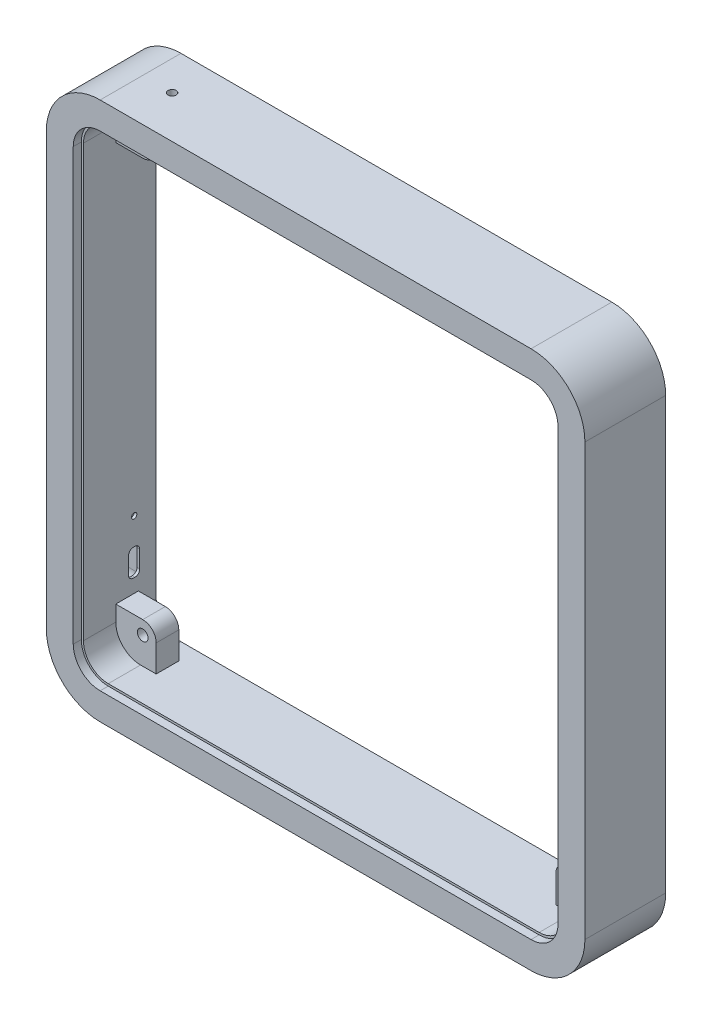
SolidWorks part; units mm, degrees
ref_plane "Piano frontale" through (0, 0, 0) normal (0, 0, 1) x (1, 0, 0)
ref_plane "Piano superiore" through (0, 0, 0) normal (0, 1, 0) x (1, 0, 0)
ref_plane "Piano destro" through (0, 0, 0) normal (1, 0, 0) x (0, 0, -1)
sketch "Sketch2" plane through (0, 0, 0) normal (0, 0, 1) x (1, 0, 0)
  line L5 (-100, -100) -> (100, -100)
  line L6 (-100, -100) -> (-100, 100)
  line L7 (-100, 100) -> (100, 100)
  line L8 (100, -100) -> (100, 100)
  line L9 (-100, -100) -> (100, 100) construction
  line L10 (-100, 100) -> (100, -100) construction
  point P0 (0, 0)
  dimension "D1" = 200
extrude "Boss-Extrude1" add sketch "Sketch2" along normal blind 30
fillet "Fillet1" radius 20 4 edges at (-100, -100, 15) (100, -100, 15) (100, 100, 15) (-100, 100, 15)
sketch "Sketch3" plane through (0, 0, 30) normal (0, 0, 1) x (1, 0, 0)
  line L8 (-90, 80) -> (-90, -80)
  line L9 (-80, -90) -> (80, -90)
  line L10 (90, -80) -> (90, 80)
  line L11 (80, 90) -> (-80, 90)
  line L12 (-90, 80) -> (-90, -80)
  line L13 (-80, -90) -> (80, -90)
  line L14 (90, -80) -> (90, 80)
  line L15 (80, 90) -> (-80, 90)
  arc A8 (-90, -80) -> (-80, -90) centre (-80, -80) ccw
  arc A9 (80, -90) -> (90, -80) centre (80, -80) ccw
  arc A10 (90, 80) -> (80, 90) centre (80, 80) ccw
  arc A11 (-80, 90) -> (-90, 80) centre (-80, 80) ccw
  arc A12 (-90, -80) -> (-80, -90) centre (-80, -80) ccw
  arc A13 (80, -90) -> (90, -80) centre (80, -80) ccw
  arc A14 (90, 80) -> (80, 90) centre (80, 80) ccw
  arc A15 (-80, 90) -> (-90, 80) centre (-80, 80) ccw
  dimension "D1" = 10
extrude "Cut-Extrude1" cut sketch "Sketch3" against normal blind 3
sketch "Sketch4" plane through (0, 0, 27) normal (0, 0, 1) x (1, 0, 0)
  line L16 (-89.2, 80) -> (-89.2, -80)
  line L17 (-80, -89.2) -> (80, -89.2)
  line L18 (89.2, -80) -> (89.2, 80)
  line L19 (80, 89.2) -> (-80, 89.2)
  line L20 (-89.2, 80) -> (-89.2, -80)
  line L21 (-80, -89.2) -> (80, -89.2)
  line L22 (89.2, -80) -> (89.2, 80)
  line L23 (80, 89.2) -> (-80, 89.2)
  arc A16 (-80, 89.2) -> (-89.2, 80) centre (-80, 80) ccw
  arc A17 (-89.2, -80) -> (-80, -89.2) centre (-80, -80) ccw
  arc A18 (80, -89.2) -> (89.2, -80) centre (80, -80) ccw
  arc A19 (89.2, 80) -> (80, 89.2) centre (80, 80) ccw
  arc A20 (-80, 89.2) -> (-89.2, 80) centre (-80, 80) ccw
  arc A21 (-89.2, -80) -> (-80, -89.2) centre (-80, -80) ccw
  arc A22 (80, -89.2) -> (89.2, -80) centre (80, -80) ccw
  arc A23 (89.2, 80) -> (80, 89.2) centre (80, 80) ccw
  dimension "D1" = 0.8
extrude "Cut-Extrude2" cut sketch "Sketch4" against normal through all
sketch "Sketch6" plane through (0, 0, 0) normal (0, 0, -1) x (-1, 0, 0)
  line L1 (-89.2, -74.2) -> (-74.2, -74.2)
  line L2 (-89.2, -74.2) -> (-89.2, -89.2)
  line L3 (-89.2, -89.2) -> (-74.2, -89.2)
  line L4 (-74.2, -74.2) -> (-74.2, -89.2)
  line L5 (-89.2, -80) -> (-89.2, 80) construction
  line L6 (80, -89.2) -> (-80, -89.2) construction
  line L18 (-74.2, 89.2) -> (-74.2, 74.2)
  line L19 (-89.2, 89.2) -> (89.2, 89.2) construction
  line L20 (-89.2, 89.2) -> (-89.2, -89.2) construction
  line L21 (-89.2, -89.2) -> (89.2, -89.2) construction
  line L22 (89.2, 89.2) -> (89.2, -89.2) construction
  line L23 (-89.2, 89.2) -> (89.2, -89.2) construction
  line L24 (-89.2, -89.2) -> (89.2, 89.2) construction
  line L25 (-74.2, 74.2) -> (-89.2, 74.2)
  line L26 (-89.2, 89.2) -> (-89.2, 74.2)
  line L27 (-74.2, 89.2) -> (-89.2, 89.2)
  line L28 (89.2, 74.2) -> (74.2, 74.2)
  line L29 (74.2, 74.2) -> (74.2, 89.2)
  line L30 (89.2, 89.2) -> (74.2, 89.2)
  line L31 (89.2, 74.2) -> (89.2, 89.2)
  line L32 (74.2, -89.2) -> (74.2, -74.2)
  line L33 (74.2, -74.2) -> (89.2, -74.2)
  line L34 (89.2, -89.2) -> (89.2, -74.2)
  line L35 (74.2, -89.2) -> (89.2, -89.2)
  point P14 (0, 0)
  point P19 (0, 0)
  point P24 (0, 0)
  point P29 (0, 0)
  dimension "D2" = 4
  dimension "D1" = 15
extrude "Boss-Extrude4" add sketch "Sketch6" against normal blind 15
fillet "Fillet2" radius 5 4 edges at (74.2, -74.2, 7.5) (-74.2, -74.2, 7.5) (-74.2, 74.2, 7.5) (74.2, 74.2, 7.5)
hole_wizard "Ø4.0 (4) Diameter Hole1" positions "Sketch8" profile "Sketch9" hole size "Ø4.0" standard "ANSI Metric" end condition through all
sketch "Sketch8" plane through (0, 0, 0) normal (0, 0, -1) x (-1, 0, 0)
  point P0 (-79.2, 79.2)
  point P3 (79.2, 79.2)
  point P6 (-79.2, -79.2)
  point P9 (79.2, -79.2)
sketch "Sketch9" plane through (79.2, 79.2, 0) normal (1, 0, 0) x (0, 1, 0)
  line L0 (0, 0) -> (0, 30)
  line L1 (0, 30) -> (2, 30)
  line L2 (2, 30) -> (2, 0)
  line L5 (2, 0) -> (0, 0)
  line L11 (0, -6.35) -> (0, 107.95) construction
  dimension "Thru Hole Dia." = 4
  dimension "Thru Hole Depth" = 30
sketch "Sketch10" plane through (0, 0, 0) normal (0, 0, -1) x (-1, 0, 0)
  line L0 (89.2, -80) -> (89.2, 80)
  line L1 (80, 89.2) -> (-80, 89.2)
  line L2 (-89.2, 80) -> (-89.2, -80)
  line L3 (-80, -89.2) -> (80, -89.2)
  line L4 (90, -80) -> (90, 80)
  line L5 (-80, -90) -> (80, -90)
  line L6 (-90, 80) -> (-90, -80)
  line L7 (80, 90) -> (-80, 90)
  line L8 (90, -80) -> (90, 80) construction
  line L9 (-80, -90) -> (80, -90) construction
  line L10 (-90, 80) -> (-90, -80) construction
  line L11 (80, 90) -> (-80, 90) construction
  arc A0 (89.2, 80) -> (80, 89.2) centre (80, 80) ccw
  arc A1 (-80, 89.2) -> (-89.2, 80) centre (-80, 80) ccw
  arc A2 (-89.2, -80) -> (-80, -89.2) centre (-80, -80) ccw
  arc A3 (80, -89.2) -> (89.2, -80) centre (80, -80) ccw
  arc A4 (90, 80) -> (80, 90) centre (80, 80) ccw
  arc A5 (80, -90) -> (90, -80) centre (80, -80) ccw
  arc A6 (-90, -80) -> (-80, -90) centre (-80, -80) ccw
  arc A7 (-80, 90) -> (-90, 80) centre (-80, 80) ccw
  arc A8 (90, 80) -> (80, 90) centre (80, 80) ccw construction
  arc A9 (80, -90) -> (90, -80) centre (80, -80) ccw construction
  arc A10 (-90, -80) -> (-80, -90) centre (-80, -80) ccw construction
  arc A11 (-80, 90) -> (-90, 80) centre (-80, 80) ccw construction
  dimension "D1" = 0
  dimension "D2" = 0.8
extrude "Cut-Extrude3" cut sketch "Sketch10" against normal blind 6.6
sketch "Sketch11" plane through (0, 100, 0) normal (0, 1, 0) x (1, 0, 0)
  circle A0 centre (-68.955, -14.3249) radius 1.5
extrude "Cut-Extrude4" cut sketch "Sketch11" against normal up to next
sketch "Sketch15" plane through (-89.2, 0, 0) normal (1, 0, 0) x (0, 0, -1)
  line L0 (-6.6, -64.1785) -> (-6.6, -64.1485) construction
  line L1 (-6.1, -64.1785) -> (-6.1, -64.1485)
  line L2 (-6.1, -64.1485) -> (-6.1, -60.9885)
  line L3 (-7.9, -59.1885) -> (-8.46, -59.1885)
  line L4 (-10.26, -60.9885) -> (-10.26, -67.3385)
  line L5 (-8.46, -69.1385) -> (-7.9, -69.1385)
  line L6 (-6.1, -67.3385) -> (-6.1, -64.1785)
  line L7 (-8.18, -49.2385) -> (-8.18, -69.1385) construction
  line L12 (-9.76, -60.9885) -> (-9.76, -67.3385)
  line L13 (-7.9, -59.6885) -> (-8.46, -59.6885)
  line L14 (-6.6, -64.1485) -> (-6.6, -60.9885)
  line L15 (-6.75, -64.1485) -> (-6.6, -64.1485)
  line L16 (-6.75, -60.9885) -> (-6.75, -64.1485)
  line L17 (-8.46, -59.8385) -> (-7.9, -59.8385)
  line L18 (-9.61, -67.3385) -> (-9.61, -60.9885)
  line L19 (-7.9, -68.4885) -> (-8.46, -68.4885)
  line L20 (-6.75, -64.1785) -> (-6.75, -67.3385)
  line L21 (-6.6, -64.1785) -> (-6.75, -64.1785)
  line L22 (-6.6, -67.3385) -> (-6.6, -64.1785)
  line L23 (-8.46, -68.6385) -> (-7.9, -68.6385)
  line L24 (-9.76, -60.9885) -> (-9.76, -67.3385) construction
  line L25 (-7.9, -59.6885) -> (-8.46, -59.6885) construction
  line L26 (-6.6, -64.1485) -> (-6.6, -60.9885) construction
  line L34 (-6.6, -67.3385) -> (-6.6, -64.1785) construction
  line L35 (-8.46, -68.6385) -> (-7.9, -68.6385) construction
  arc A0 (-6.1, -60.9885) -> (-6.6272, -59.7157) centre (-7.9, -60.9885) ccw
  arc A1 (-6.6272, -59.7157) -> (-7.9, -59.1885) centre (-7.9, -60.9885) ccw
  arc A2 (-8.46, -59.1885) -> (-9.7328, -59.7157) centre (-8.46, -60.9885) ccw
  arc A3 (-9.7328, -59.7157) -> (-10.26, -60.9885) centre (-8.46, -60.9885) ccw
  arc A4 (-10.26, -67.3385) -> (-9.7328, -68.6112) centre (-8.46, -67.3385) ccw
  arc A5 (-9.7328, -68.6112) -> (-8.46, -69.1385) centre (-8.46, -67.3385) ccw
  arc A6 (-7.9, -69.1385) -> (-6.6272, -68.6112) centre (-7.9, -67.3385) ccw
  arc A7 (-6.6272, -68.6112) -> (-6.1, -67.3385) centre (-7.9, -67.3385) ccw
  circle A9 centre (-8.18, -49.2385) radius 1
  arc A16 (-9.3792, -68.2577) -> (-8.46, -68.6385) centre (-8.46, -67.3385) ccw
  arc A17 (-9.76, -67.3385) -> (-9.3792, -68.2577) centre (-8.46, -67.3385) ccw
  arc A18 (-9.3792, -60.0692) -> (-9.76, -60.9885) centre (-8.46, -60.9885) ccw
  arc A19 (-8.46, -59.6885) -> (-9.3792, -60.0692) centre (-8.46, -60.9885) ccw
  arc A20 (-6.9808, -60.0692) -> (-7.9, -59.6885) centre (-7.9, -60.9885) ccw
  arc A21 (-6.6, -60.9885) -> (-6.9808, -60.0692) centre (-7.9, -60.9885) ccw
  arc A22 (-6.75, -60.9885) -> (-7.0868, -60.1753) centre (-7.9, -60.9885) ccw
  arc A23 (-7.0868, -60.1753) -> (-7.9, -59.8385) centre (-7.9, -60.9885) ccw
  arc A24 (-8.46, -59.8385) -> (-9.2732, -60.1753) centre (-8.46, -60.9885) ccw
  arc A25 (-9.2732, -60.1753) -> (-9.61, -60.9885) centre (-8.46, -60.9885) ccw
  arc A26 (-9.61, -67.3385) -> (-9.2732, -68.1516) centre (-8.46, -67.3385) ccw
  arc A27 (-9.2732, -68.1516) -> (-8.46, -68.4885) centre (-8.46, -67.3385) ccw
  arc A28 (-7.9, -68.4885) -> (-7.0868, -68.1516) centre (-7.9, -67.3385) ccw
  arc A29 (-7.0868, -68.1516) -> (-6.75, -67.3385) centre (-7.9, -67.3385) ccw
  arc A30 (-6.9808, -68.2577) -> (-6.6, -67.3385) centre (-7.9, -67.3385) ccw
  arc A31 (-7.9, -68.6385) -> (-6.9808, -68.2577) centre (-7.9, -67.3385) ccw
  arc A32 (-9.3792, -68.2577) -> (-8.46, -68.6385) centre (-8.46, -67.3385) ccw construction
  arc A33 (-9.76, -67.3385) -> (-9.3792, -68.2577) centre (-8.46, -67.3385) ccw construction
  arc A34 (-9.3792, -60.0692) -> (-9.76, -60.9885) centre (-8.46, -60.9885) ccw construction
  arc A35 (-8.46, -59.6885) -> (-9.3792, -60.0692) centre (-8.46, -60.9885) ccw construction
  arc A36 (-6.9808, -60.0692) -> (-7.9, -59.6885) centre (-7.9, -60.9885) ccw construction
  arc A37 (-6.6, -60.9885) -> (-6.9808, -60.0692) centre (-7.9, -60.9885) ccw construction
  arc A46 (-6.9808, -68.2577) -> (-6.6, -67.3385) centre (-7.9, -67.3385) ccw construction
  arc A47 (-7.9, -68.6385) -> (-6.9808, -68.2577) centre (-7.9, -67.3385) ccw construction
  point P73 (-8.18, -59.6885)
  point P74 (-8.18, -59.1885)
  dimension "D3" = 2
  dimension "D1" = 0
  dimension "D2" = 0.5
extrude "Cut-Extrude5" cut sketch "Sketch15" against normal through all
sketch "Sketch16" plane through (-100, 0, 0) normal (-1, 0, 0) x (0, 0, 1)
  line L0 (6.1, -67.3385) -> (6.1, -60.9885) construction
  line L1 (7.9, -59.1885) -> (8.46, -59.1885) construction
  line L2 (10.26, -60.9885) -> (10.26, -67.3385) construction
  line L3 (8.46, -69.1385) -> (7.9, -69.1385) construction
  line L4 (6.1, -67.3385) -> (6.1, -60.9885) construction
  line L5 (7.9, -59.1885) -> (8.46, -59.1885) construction
  line L6 (10.26, -60.9885) -> (10.26, -67.3385) construction
  line L7 (8.46, -69.1385) -> (7.9, -69.1385) construction
  line L8 (3.1, -67.3385) -> (3.1, -60.9885)
  line L9 (7.9, -56.1885) -> (8.46, -56.1885)
  line L10 (13.26, -60.9885) -> (13.26, -67.3385)
  line L11 (8.46, -72.1385) -> (7.9, -72.1385)
  arc A0 (7.9, -59.1885) -> (6.1, -60.9885) centre (7.9, -60.9885) ccw construction
  arc A1 (10.26, -60.9885) -> (8.46, -59.1885) centre (8.46, -60.9885) ccw construction
  arc A2 (8.46, -69.1385) -> (10.26, -67.3385) centre (8.46, -67.3385) ccw construction
  arc A3 (6.1, -67.3385) -> (7.9, -69.1385) centre (7.9, -67.3385) ccw construction
  arc A4 (7.9, -59.1885) -> (6.1, -60.9885) centre (7.9, -60.9885) ccw construction
  arc A5 (10.26, -60.9885) -> (8.46, -59.1885) centre (8.46, -60.9885) ccw construction
  arc A6 (8.46, -69.1385) -> (10.26, -67.3385) centre (8.46, -67.3385) ccw construction
  arc A7 (6.1, -67.3385) -> (7.9, -69.1385) centre (7.9, -67.3385) ccw construction
  arc A8 (7.9, -56.1885) -> (3.1, -60.9885) centre (7.9, -60.9885) ccw
  arc A9 (13.26, -60.9885) -> (8.46, -56.1885) centre (8.46, -60.9885) ccw
  arc A10 (8.46, -72.1385) -> (13.26, -67.3385) centre (8.46, -67.3385) ccw
  arc A11 (3.1, -67.3385) -> (7.9, -72.1385) centre (7.9, -67.3385) ccw
  dimension "D1" = 3
sketch "Sketch17" plane through (-100, 0, 0) normal (-1, 0, 0) x (0, 0, 1)
  line L0 (30, -48.3269) -> (0, -48.3269) construction
  line L1 (15.0613, -39.8475) -> (7.5, -39.8475)
  line L2 (2.5, -44.8475) -> (2.5, -72.5)
  line L3 (7.5, -77.5) -> (15.0613, -77.5)
  line L4 (0, 80) -> (0, -80)
  line L5 (0, -80) -> (30, -80)
  line L6 (30, -80) -> (30, 80)
  line L7 (30, 80) -> (0, 80)
  line L8 (0, -48.3269) -> (0, -80) construction
  line L9 (0, -80) -> (30, -80) construction
  line L10 (30, -80) -> (30, -48.3269) construction
  line L12 (20.0613, -72.5) -> (20.0613, -44.8475)
  line L13 (0, 80) -> (0, -80) construction
  arc A0 (7.5, -39.8475) -> (2.5, -44.8475) centre (7.5, -44.8475) ccw
  arc A1 (15.0613, -39.8475) -> (20.0613, -44.8475) centre (15.0613, -44.8475) cw
  arc A2 (2.5, -72.5) -> (7.5, -77.5) centre (7.5, -72.5) ccw
  arc A3 (15.0613, -77.5) -> (20.0613, -72.5) centre (15.0613, -72.5) ccw
  dimension "D5" = 5
  dimension "D4" = 2.5
  dimension "D2" = 10.8615
  dimension "D3" = 10.8615
  dimension "D6" = 2.5
  dimension "D1" = 0
extrude "Cut-Extrude7" cut sketch "Sketch17" against normal offset from surface (9.8 mm away) 1 up to face at (-89.2, -64.1635, 8.18)
fillet "Fillet3" radius 1 16 edges at (-90.2, -77.5, 11.2807) (-90.2, -76.0355, 18.5969) (-90.2, -58.6738, 20.0613) (-90.2, -41.312, 18.5969) (-90.2, -39.8475, 11.2807) (-90.2, -41.312, 3.9645) (-90.2, -58.6738, 2.5) (-100, -58.6738, 2.5) (-100, -41.312, 3.9645) (-100, -39.8475, 11.2807) (-100, -41.312, 18.5969) (-100, -58.6738, 20.0613) (-100, -76.0355, 18.5969) (-100, -77.5, 11.2807) (-90.2, -76.0355, 3.9645) (-100, -76.0355, 3.9645)
